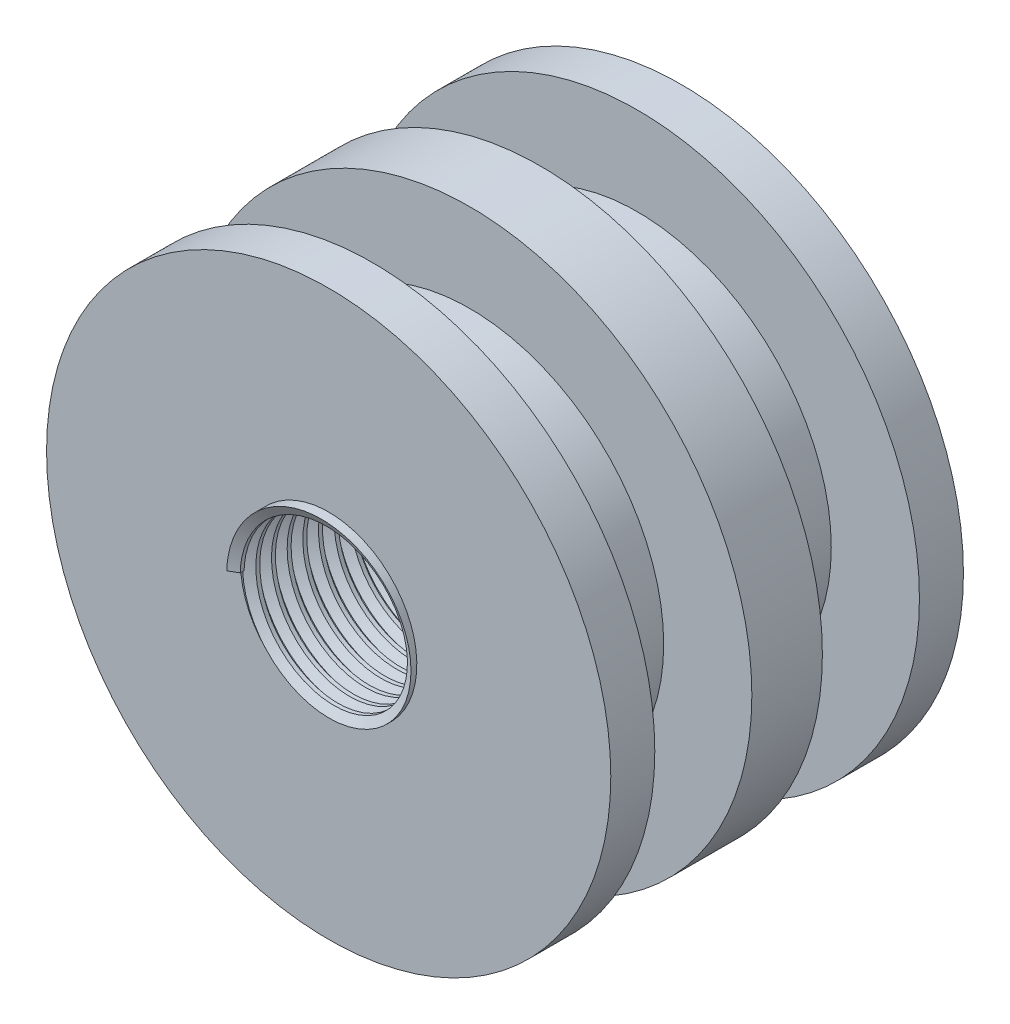
SolidWorks part; units mm, degrees
material "1060 Alloy"
ref_plane "Front Plane" through (0, 0, 0) normal (0, 0, 1) x (1, 0, 0)
ref_plane "Top Plane" through (0, 0, 0) normal (0, 1, 0) x (1, 0, 0)
ref_plane "Right Plane" through (0, 0, 0) normal (1, 0, 0) x (0, 0, -1)
sketch "Sketch1" plane through (0, 0, 0) normal (1, 0, 0) x (0, 0, -1)
  line L0 (-9.9845, 0) -> (10.9036, 0) construction
  line L1 (-15.875, 0) -> (15.875, 0)
  line L2 (15.875, 0) -> (15.875, 25.4)
  line L3 (15.875, 25.4) -> (11.9126, 25.4)
  line L4 (11.9126, 25.4) -> (11.9126, 17.4625)
  line L5 (11.9126, 17.4625) -> (3.175, 17.4625)
  line L6 (3.175, 17.4625) -> (3.175, 25.4)
  line L7 (3.175, 25.4) -> (-3.175, 25.4)
  line L8 (-3.175, 25.4) -> (-3.175, 17.4625)
  line L9 (-3.175, 17.4625) -> (-11.9126, 17.4625)
  line L10 (-11.9126, 17.4625) -> (-11.9126, 25.4)
  line L11 (-11.9126, 25.4) -> (-15.875, 25.4)
  line L12 (-15.875, 25.4) -> (-15.875, 0)
  point P3 (0, 0)
  point P17 (7.5438, 17.4625)
  dimension "D1" = 6.35
  dimension "D2" = 3.9624
  dimension "D3" = 50.8
  dimension "D4" = 34.925
  dimension "D5" = 8.7376
revolve "Revolve1" add sketch "Sketch1" angle 360 about L0
hole_wizard "#97 (0.625) Diameter Hole1" positions "Sketch2" profile "Sketch3" hole size "#97" standard "ANSI Inch" end condition through all
sketch "Sketch2" plane through (0, 0, 15.875) normal (0, 0, 1) x (1, 0, 0)
  point P0 (0, 0)
sketch "Sketch3" plane through (0, 0, 15.875) normal (1, 0, 0) x (0, -1, 0)
  line L0 (0, 0) -> (0, 31.75)
  line L1 (0, 31.75) -> (7.9375, 31.75)
  line L2 (7.9375, 31.75) -> (7.9375, 0)
  line L5 (7.9375, 0) -> (0, 0)
  line L11 (0, -6.35) -> (0, 107.95) construction
  dimension "Thru Hole Dia." = 15.875
  dimension "Thru Hole Depth" = 31.75
thread "Thread1" pitch 1.4111 start angle 0, offset 0, length 31.75, pitch 1.4111, diameter 15.875
ref_plane "Plane1" through (7.9375, 0, -15.875) normal (0, -1, 0) x (1, 0, 0)
sketch "Thread Profile1" plane through (7.9375, 0, -15.875) normal (0, -1, 0) x (1, 0, 0)
  line L0 (0, 0) -> (0, 1.4111) construction
  line L11 (0, 0) -> (0, 1.2347)
  line L12 (0, 1.2347) -> (-0.7638, 0.7937)
  line L13 (-0.7638, 0.7937) -> (-0.7638, 0.441)
  line L15 (-0.7638, 0.441) -> (0, 0)
  line L17 (-0.7638, 0.6174) -> (0, 0.6174) construction
  point P2 (0, 0)
  dimension "Pitch" = 1.4111
  dimension "Profile_Angle" = 60
  dimension "Profile_Land" = 0.3528
  dimension "Profile_Height" = 0.7638
